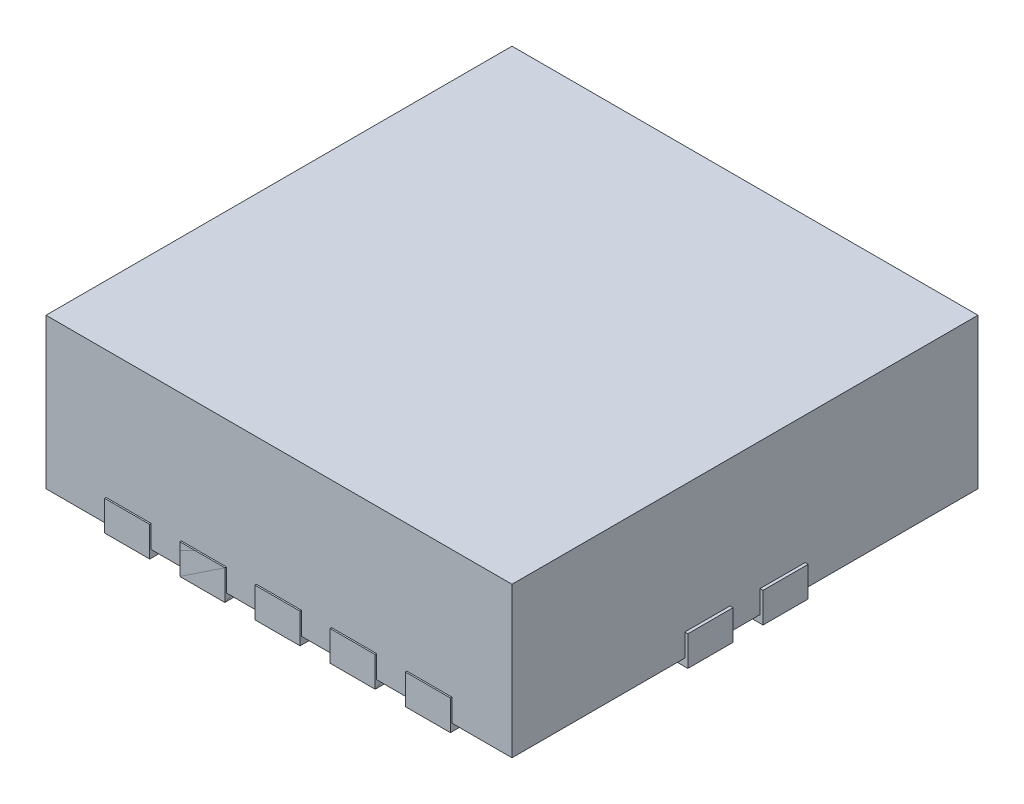
SolidWorks part; units mm, degrees
ref_plane "Front Plane" through (0, 0, 0) normal (0, 0, 1) x (1, 0, 0)
ref_plane "Top Plane" through (0, 0, 0) normal (0, 1, 0) x (1, 0, 0)
ref_plane "Right Plane" through (0, 0, 0) normal (1, 0, 0) x (0, 0, -1)
sketch "Sketch1" plane through (0, 0, 0) normal (0, 1, 0) x (1, 0, 0)
  line L1 (0, 0) -> (3.1, 0)
  line L2 (0, 0) -> (0, 3.1)
  line L3 (0, 3.1) -> (3.1, 3.1)
  line L4 (3.1, 0) -> (3.1, 3.1)
  dimension "D1" = 3.1
  dimension "D2" = 3.1
extrude "Boss-Extrude1" add sketch "Sketch1" along normal blind 1
sketch "Sketch2" plane through (0, 0, 0) normal (0, -1, 0) x (1, 0, 0)
  line L0 (1.7, 0.01) -> (1.7, -0.4)
  line L1 (1.4, 0.01) -> (1.7, 0.01)
  line L7 (1.4, 0.01) -> (1.4, -0.4)
  arc A0 (1.4, -0.4) -> (1.7, -0.4) centre (1.55, -0.3375) ccw
extrude "Boss-Extrude2" add sketch "Sketch2" against normal blind 0.2 from offset 0.05 separate body
ref_plane "Plane1" through (0, 0, -1.55) normal (0, 0, 1) x (1, 0, 0)
sketch "Sketch4" plane through (0, 0, 0) normal (0, -1, 0) x (1, 0, 0)
  line L0 (1.4, -3.11) -> (1.4, -2.7)
  line L1 (1.7, -3.11) -> (1.4, -3.11)
  line L2 (1.7, -3.11) -> (1.7, -2.7)
  arc A0 (1.7, -2.7) -> (1.4, -2.7) centre (1.55, -2.7625) ccw
extrude "Boss-Extrude3" add sketch "Sketch4" against normal blind 0.2 from offset 0.05 separate body
sketch "Sketch5" plane through (0, 0, 0) normal (0, -1, 0) x (1, 0, 0)
  line L2 (-0.01, -1.15) -> (0.4, -1.15)
  line L3 (-0.01, -1.45) -> (-0.01, -1.15)
  line L4 (-0.01, -1.45) -> (0.4, -1.45)
  arc A0 (0.4, -1.45) -> (0.4, -1.15) centre (0.3375, -1.3) ccw
extrude "Boss-Extrude4" add sketch "Sketch5" against normal blind 0.2 from offset 0.05 separate body
pattern_linear "LPattern3" count 2 spacing 0.5 along (0, 0, -1) of "Boss-Extrude4"
ref_plane "Plane2" through (1.555, 0, 0) normal (1, 0, 0) x (0, 0, -1)
mirror "Mirror7" about plane through (1.555, 0, 0) normal (1, 0, 0) of "LPattern3", "Boss-Extrude4"
pattern_linear "LPattern4" count 3 spacing 0.5 along (1, 0, 0) count 3 spacing 0.5 along (-1, 0, 0) of "Boss-Extrude2"
pattern_linear "LPattern5" count 3 spacing 0.5 along (1, 0, 0) count 3 spacing 0.5 along (-1, 0, 0) of "Boss-Extrude3"
sketch "Sketch6" plane through (0, 0, 0) normal (0, -1, 0) x (1, 0, 0)
  line L0 (0.6846, -0.725) -> (0.355, -1.0546)
  line L2 (1.555, -0.5775) -> (1.555, 0.5775) construction
  line L4 (0.6846, -0.725) -> (1.555, -0.725)
  line L5 (0.355, -1.0546) -> (0.355, -2.375)
  line L7 (0.355, -2.375) -> (2.755, -2.375)
  line L8 (2.755, -2.375) -> (2.755, -0.725)
  line L9 (2.755, -0.725) -> (1.555, -0.725)
extrude "Boss-Extrude5" add sketch "Sketch6" along normal blind 0.05
